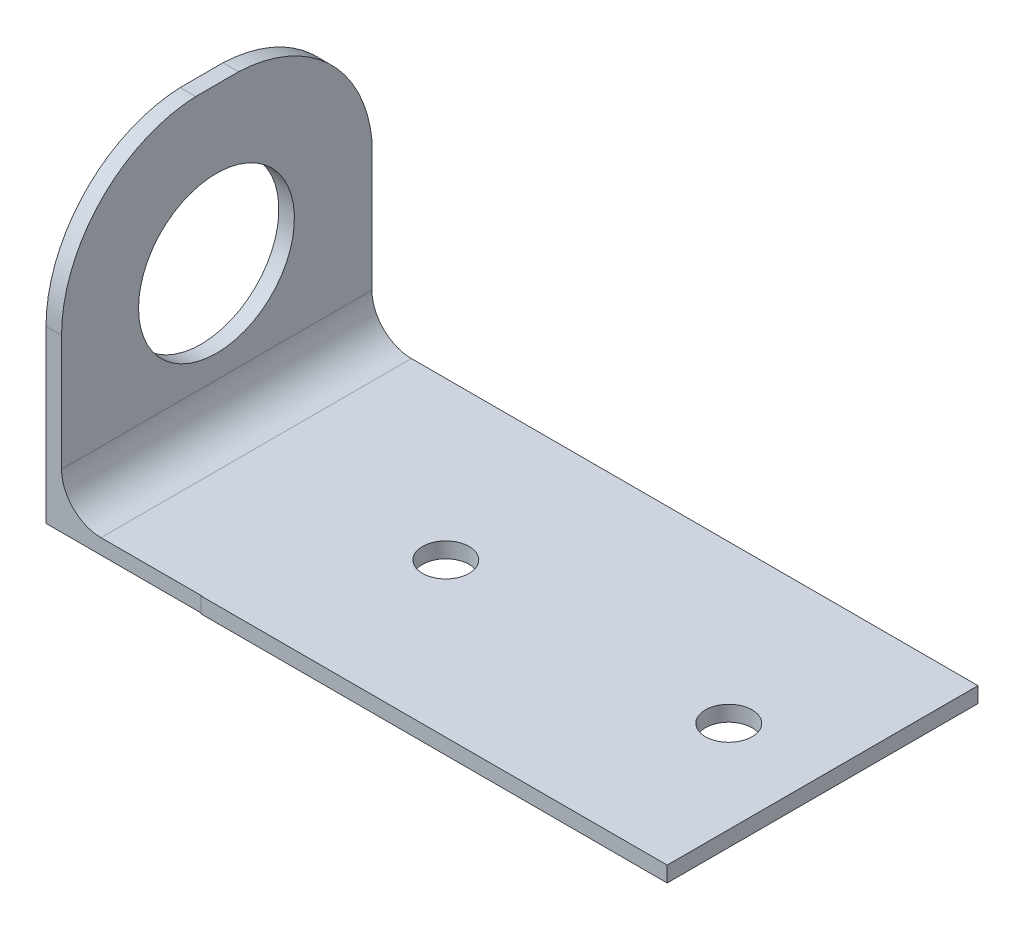
SolidWorks part; units mm, degrees
material "AISI 304"
ref_plane "Front" through (0, 0, 0) normal (0, 0, 1) x (1, 0, 0)
ref_plane "Top" through (0, 0, 0) normal (0, 1, 0) x (1, 0, 0)
ref_plane "Right" through (0, 0, 0) normal (1, 0, 0) x (0, 0, -1)
sketch "Sketch1" plane through (0, 0, 0) normal (0, 0, 1) x (1, 0, 0)
  line L0 (1, 20) -> (1, 1)
  line L1 (0, 0) -> (40, 0)
  line L2 (0, 0) -> (0, 20)
  line L3 (0, 20) -> (1, 20)
  line L4 (40, 0) -> (40, 1)
  line L5 (1, 1) -> (40, 1)
  dimension "D1" = 20
  dimension "D2" = 40
  dimension "D3" = 1
  dimension "D4" = 1
extrude "Extrude1" add sketch "Sketch1" along normal blind 20
fillet "Fillet1" radius 2.54 1 edges at (1, 1, 10)
ref_plane "Plane2" through (0, 20, 0) normal (0, 0, -1) x (-1, 0, 0)
sketch "Sketch8" plane through (0, 0, 0) normal (-1, 0, 0) x (0, 0, 1)
  line L0 (-0.0753, 19.888) -> (-0.0376, 19.8884)
  line L2 (-0.0376, 20.0013) -> (-0.0376, -0.0042)
  line L3 (-0.0376, -0.0042) -> (20.0057, -0.0042)
  line L4 (20.0057, 20.0013) -> (20.0057, -0.0042)
  circle A0 centre (10.0029, 10.0363) radius 5.0147
extrude "Cut-Extrude2" cut sketch "Sketch8" against normal blind 10 contours A0 region at (0, 10.0363, 10.0029)
sketch "Sketch9" plane through (0, 0, 0) normal (-1, 0, 0) x (0, 0, 1)
  line L0 (8.9632, 19.97) -> (8.1294, 19.97)
  line L1 (8.9524, 20.0077) -> (10.9722, 20.0077)
  line L2 (-0.0476, 11.0077) -> (-0.0476, 0.0255)
  line L3 (-0.0476, 0.0255) -> (19.9722, 0.0255)
  line L4 (19.9722, 11.0077) -> (19.9722, 0.0255)
  line L5 (8.9944, 19.9792) -> (8.2708, 19.9818)
  line L6 (19.9959, 10.9824) -> (20.0144, 20.1093)
  line L7 (20.0144, 20.1093) -> (10.9429, 20.054)
  line L8 (-0.0332, 11.0922) -> (-0.0154, 20.0918)
  line L9 (-0.0154, 20.0918) -> (9.002, 20.0025)
  arc A0 (10.9722, 20.0077) -> (19.9722, 11.0077) centre (10.9722, 11.0077) cw
  arc A1 (8.9524, 20.0077) -> (-0.0476, 11.0077) centre (8.9524, 11.0077) ccw
  line M8 (0, 20) -> (0, 0)
  line M9 (0, 0) -> (20, 0)
  line M10 (20, 0) -> (20, 20)
  line M11 (20, 20) -> (0, 20)
  dimension "D1" = 9
  dimension "D2" = 9
extrude "Cut-Extrude5" cut sketch "Sketch9" against normal blind 10 contours A0 L4 L3 M11 M8 M9 M10 | A1 M11 M8 region at (0, 17.2499, 17.8106) region at (0, 18.041, 2.0001)
sketch "Sketch10" plane through (0, 1, 0) normal (0, 1, 0) x (1, 0, 0)
  line L0 (39.9943, -0.0315) -> (39.996, -10.033)
  line L1 (3.531, -0.0112) -> (40.0866, -0.0112)
  line L2 (3.531, -0.0112) -> (3.531, -19.9422)
  line L3 (3.531, -19.9422) -> (40.0866, -19.9422)
  line L4 (40.0866, -0.0112) -> (40.0866, -19.9422)
  line L5 (15.9645, -10.1164) -> (34.6382, -10.163)
  line L7 (31.9134, -0.0112) -> (31.9135, -0.002)
  circle A2 centre (15.8714, -10.1164) radius 1.5
  circle A3 centre (34.6847, -10.163) radius 1.5
  dimension "D3" = 3
  dimension "D4" = 3
  dimension "D1" = 36.5556
  dimension "D2" = 19.931
extrude "Cut-Extrude6" cut sketch "Sketch10" against normal blind 10 contours A2 region at (15.8714, 1, 10.1164)
sketch "Sketch11" plane through (0, 1, 0) normal (0, 1, 0) x (1, 0, 0)
  line L0 (15.918, -10.0699) -> (34.1725, -10.1164)
  circle A0 centre (34.0794, -10.1164) radius 1.5
  dimension "D1" = 3
extrude "Cut-Extrude7" cut sketch "Sketch11" against normal blind 30 contours A0 region at (34.0794, 1, 10.1164)
